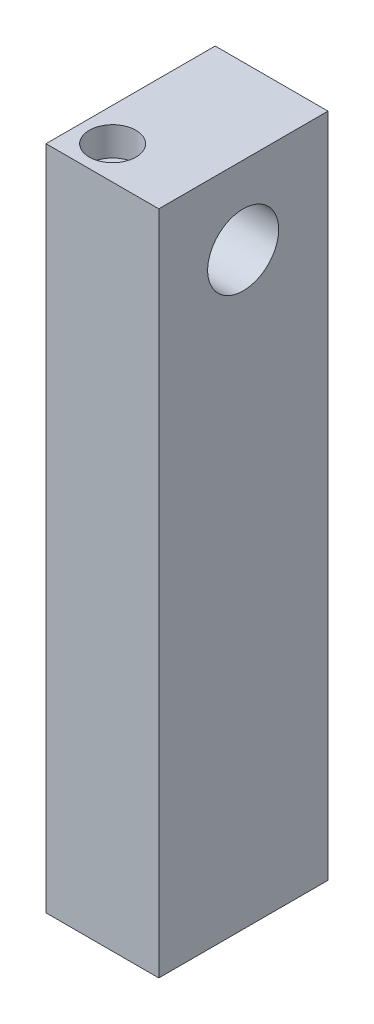
SolidWorks part; units mm, degrees
ref_plane "Front Plane" through (0, 0, 0) normal (0, 0, 1) x (1, 0, 0)
ref_plane "Top Plane" through (0, 0, 0) normal (0, 1, 0) x (1, 0, 0)
ref_plane "Right Plane" through (0, 0, 0) normal (1, 0, 0) x (0, 0, -1)
sketch "Sketch1" plane through (0, 0, 0) normal (0, 1, 0) x (1, 0, 0)
  line L1 (0, 0) -> (50.8, 0)
  line L2 (0, 0) -> (0, 76.2)
  line L3 (0, 76.2) -> (50.8, 76.2)
  line L4 (50.8, 0) -> (50.8, 76.2)
  dimension "D1" = 50.8
  dimension "D2" = 76.2
extrude "Boss-Extrude1" add sketch "Sketch1" along normal blind 300
sketch "Sketch2" plane through (50.8, 0, 0) normal (1, 0, 0) x (0, 0, -1)
  line L1 (0, 0) -> (38, 0)
  line L2 (0, 0) -> (0, 265)
  line L3 (0, 265) -> (38, 265)
  line L4 (38, 0) -> (38, 265)
  circle A0 centre (38, 265) radius 16
  dimension "D1" = 38
  dimension "D2" = 265
extrude "Cut-Extrude1" cut sketch "Sketch2" against normal blind 150 contours L4 A0 L3 | L3 A0 L4 region at (50.8, 258.2094, -31.2094) region at (50.8, 267.2635, -40.2635)
sketch "Sketch4" plane through (0, 300, 0) normal (0, 1, 0) x (1, 0, 0)
  line L5 (50.8, 0) -> (15, 0)
  line L6 (50.8, 0) -> (50.8, 15)
  line L7 (50.8, 15) -> (15, 15)
  line L8 (15, 0) -> (15, 15)
  circle A0 centre (15, 15) radius 5.25
  dimension "D1" = 35.8
  dimension "D2" = 15
extrude "Cut-Extrude3" cut sketch "Sketch4" against normal blind 50 contours A0
sketch "Sketch6" plane through (0, 300, 0) normal (0, 1, 0) x (1, 0, 0)
  circle A1 centre (15, 15) radius 10.5
extrude "Cut-Extrude4" cut sketch "Sketch6" against normal blind 13
